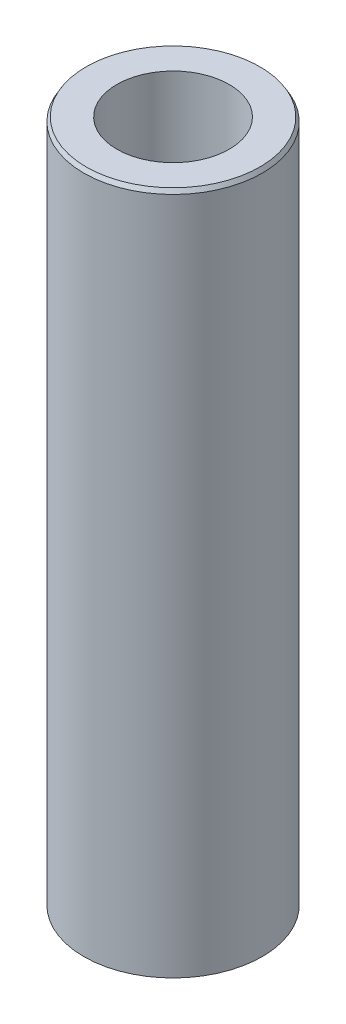
SolidWorks part; units mm, degrees
ref_plane "Front Plane" through (0, 0, 0) normal (0, 0, 1) x (1, 0, 0)
ref_plane "Top Plane" through (0, 0, 0) normal (0, 1, 0) x (1, 0, 0)
ref_plane "Right Plane" through (0, 0, 0) normal (1, 0, 0) x (0, 0, -1)
sketch "Sketch1" plane through (0, 0, 0) normal (0, 1, 0) x (1, 0, 0)
  circle A0 centre (0, 0) radius 52.5
  dimension "SHAFT_OD" = 105
extrude "Boss-Extrude1" add sketch "Sketch1" along normal blind 403.0436
sketch "Sketch2" plane through (0, 0, 0) normal (0, 1, 0) x (1, 0, 0)
  circle A0 centre (0, 0) radius 33.0451
  dimension "BORE_D" = 66.0901
extrude "Cut-Extrude1" cut sketch "Sketch2" along normal through all
chamfer "Chamfer1" distance 2.4357 angle 30 2 edges at (0, 403.0436, 52.5) (0, 0, 52.5) first distance on face at (0, 403.0436, 52.5) first distance on face at (0, 0, 33.0451)
